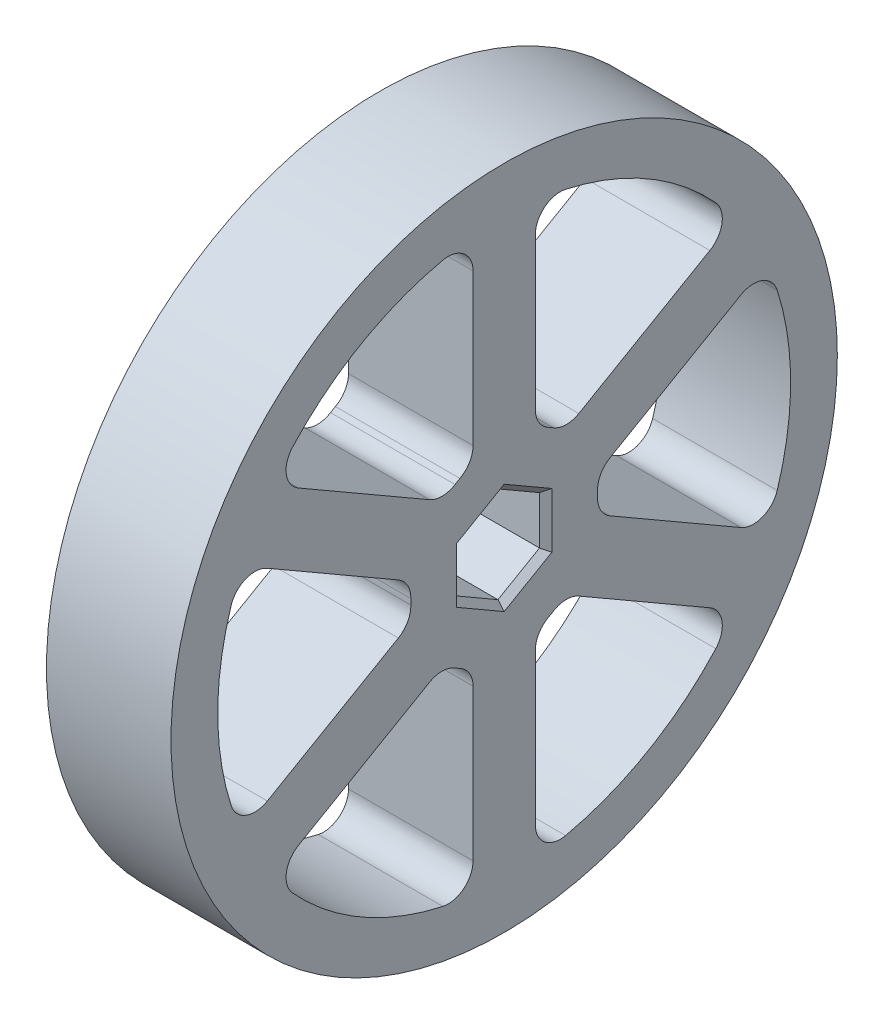
SolidWorks part; units mm, degrees
ref_plane "Front Plane" through (0, 0, 0) normal (0, 0, 1) x (1, 0, 0)
ref_plane "Top Plane" through (0, 0, 0) normal (0, 1, 0) x (1, 0, 0)
ref_plane "Right Plane" through (0, 0, 0) normal (1, 0, 0) x (0, 0, -1)
sketch "Axle Profile" plane through (0, 0, 0) normal (1, 0, 0) x (0, 0, -1)
  line L1 (0, -4.8895) -> (4.2344, -2.4448)
  line L2 (4.2344, -2.4448) -> (4.2344, 2.4447)
  line L3 (4.2344, 2.4447) -> (0, 4.8895)
  line L4 (0, 4.8895) -> (-4.2344, 2.4448)
  line L5 (-4.2344, 2.4448) -> (-4.2344, -2.4448)
  line L6 (-4.2344, -2.4448) -> (0, -4.8895)
  circle A0 centre (0, 0) radius 4.8895 construction
  circle A1 centre (0, 0) radius 9.525
  dimension "D1" = 9.779
  dimension ".625" = 19.05
extrude "Wheel Hub" add sketch "Axle Profile" along normal blind 12.7
fillet "Hub Fillet" [suppressed] radius 2.032
ref_plane "Spoke Plane" through (0, 0, -4.2344) normal (0, 0, 1) x (1, 0, 0)
sketch "Sketch2" plane through (0, 0, -4.2344) normal (0, 0, 1) x (1, 0, 0)
  line L0 (12.7, 2.4448) -> (0, -2.4447) construction
  line L1 (0, 2.4448) -> (12.7, -2.4447) construction
  circle A0 centre (6.35, 0) radius 2.54
  dimension "D1" = 5.08
extrude "Spoke" [suppressed] add sketch "Sketch2" against normal blind 25.4
ref_axis "Pattern Axis" through (12.7, 0, 0) along (-1, 0, 0)
pattern_circular "CirPattern1" [suppressed] count 6 over 360 about axis through (12.7, 0, 0) along (-1, 0, 0) of bodies 102
fillet "Hub/Spoke Fillet" [suppressed] radius 2.54
ref_plane "Mid Plane" through (6.35, 0, 0) normal (-1, 0, 0) x (0, 0, 1)
sketch "Sketch3" plane through (6.35, 0, 0) normal (-1, 0, 0) x (0, 0, 1)
  circle A0 centre (0, 0) radius 29.21
  circle A1 centre (0, 0) radius 33.9725
  dimension "D1" = 58.42
  dimension "D2" = 67.945
extrude "Wheel Rim" add sketch "Sketch3" along normal up to surface and the other way up to surface up to face at (0, 0, -9.525) other way up to face at (12.7, 0, -9.525)
fillet "Rim/Spoke Fillet" [suppressed] radius 2.54
fillet "Rim Fillet" [suppressed] radius 0.762
sketch "Sketch4" plane through (12.7, 0, 0) normal (1, 0, 0) x (0, 0, -1)
  line L0 (0, 8.9803) -> (0, 0) construction
  line L1 (-3.175, 8.9803) -> (3.175, 8.9803)
  line L2 (-3.175, 8.9803) -> (-3.175, 29.21)
  line L3 (-3.175, 29.21) -> (3.175, 29.21)
  line L4 (3.175, 8.9803) -> (3.175, 29.21)
  circle A0 centre (0, 0) radius 9.525 construction
  circle A1 centre (0, 0) radius 29.21 construction
  dimension "D1" = 6.35
extrude "Boss-Extrude1" add sketch "Sketch4" against normal up to surface (12.7 mm away) up to face at (0, 0, -29.21)
pattern_circular "Spokes" count 6 over 360 about axis through (0, 0, 0) along (1, 0, 0) of "Boss-Extrude1"
fillet "Spoke Fillets" radius 2.54 24 edges at (6.35, 8.9803, 3.175) (6.35, 7.2398, 6.1896) (6.35, -1.7405, 9.3646) (6.35, 1.7405, 9.3646) (6.35, -8.9803, 3.175) (6.35, -7.2398, 6.1896) (6.35, -8.9803, -3.175) (6.35, -7.2398, -6.1896) (6.35, -1.7405, -9.3646) (6.35, 1.7405, -9.3646) (6.35, 7.2398, -6.1896) (6.35, 8.9803, -3.175) (6.35, 29.0369, -3.175) (6.35, 29.0369, 3.175) (6.35, 17.2681, 23.5592) (6.35, 11.7688, 26.7342) (6.35, -11.7688, 26.7342) (6.35, -17.2681, 23.5592) (6.35, -29.0369, 3.175) (6.35, -17.2681, -23.5592) (6.35, -11.7688, -26.7342) (6.35, 11.7688, -26.7342) (6.35, 17.2681, -23.5592) (6.35, -29.0369, -3.175)
chamfer "Shaft Chamfers" distance 0.635 angle 45 12 edges at (0, 0, 4.2344) (0, 3.6671, 2.1172) (0, 3.6671, -2.1172) (0, 0, -4.2344) (0, -3.6671, -2.1172) (0, -3.6671, 2.1172) (12.7, -3.6671, -2.1172) (12.7, -3.6671, 2.1172) (12.7, 0, 4.2344) (12.7, 3.6671, 2.1172) (12.7, 3.6671, -2.1172) (12.7, 0, -4.2344)
